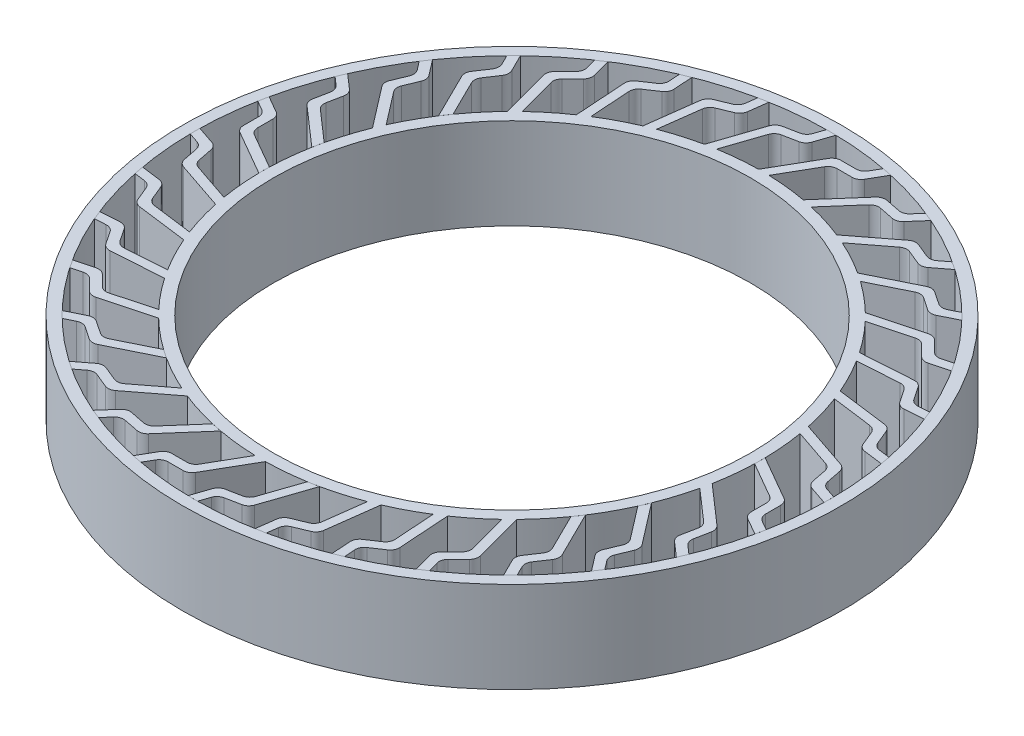
SolidWorks part; units mm, degrees
ref_plane "Alzado" through (0, 0, 0) normal (0, 0, 1) x (1, 0, 0)
ref_plane "Planta" through (0, 0, 0) normal (0, 1, 0) x (1, 0, 0)
ref_plane "Vista lateral" through (0, 0, 0) normal (1, 0, 0) x (0, 0, -1)
sketch "Croquis1" plane through (0, 0, 0) normal (0, 1, 0) x (1, 0, 0)
  line L0 (0, 279.5) -> (0, -279.5) construction
  line L1 (-279.5, 0) -> (279.5, 0) construction
  line L2 (-2.8965, 219.4809) -> (6.296, 219.4097)
  line L3 (51.4013, 274.7329) -> (59.6687, 273.0566)
  line L4 (-2.8965, 219.4809) -> (19.5628, 258.4505)
  line L5 (51.257, 258.4611) -> (59.6687, 273.0566)
  line L6 (51.4013, 274.7329) -> (46.6341, 266.4611)
  line L7 (39.7028, 262.4558) -> (26.4941, 262.4558)
  line L8 (104.0114, 259.4261) -> (111.7929, 256.1691)
  line L9 (100.6953, 243.4952) -> (111.7929, 256.1691)
  line L10 (44.3257, 254.4558) -> (31.117, 254.4558)
  line L11 (24.1857, 250.4505) -> (6.296, 219.4097)
  line L12 (93.1159, 240.919) -> (80.1609, 243.4959)
  line L13 (72.5814, 240.9198) -> (48.9797, 213.9655)
  line L14 (39.9778, 215.8287) -> (48.9797, 213.9655)
  line L15 (39.9778, 215.8287) -> (69.6081, 249.6679)
  line L16 (90.1425, 249.6672) -> (77.1876, 252.2441)
  line L17 (104.0114, 259.4261) -> (97.722, 252.2433)
  line L18 (152.6243, 234.1497) -> (159.6209, 229.4372)
  line L19 (146.2641, 219.1718) -> (159.6209, 229.4372)
  line L20 (138.3276, 218.1238) -> (126.1243, 223.1786)
  line L21 (118.1879, 222.1306) -> (89.7812, 200.2987)
  line L22 (81.3157, 203.8823) -> (89.7812, 200.2987)
  line L23 (81.3157, 203.8823) -> (116.9784, 231.2908)
  line L24 (137.1181, 227.284) -> (124.9148, 232.3387)
  line L25 (152.6243, 234.1497) -> (145.0545, 228.3319)
  line L26 (195.372, 199.875) -> (201.3148, 193.8881)
  line L27 (186.2119, 186.4257) -> (201.3148, 193.8881)
  line L28 (178.2235, 186.9463) -> (167.2409, 194.2846)
  line L29 (159.2525, 194.8051) -> (127.1324, 178.9346)
  line L30 (119.5287, 184.1009) -> (127.1324, 178.9346)
  line L31 (119.5287, 184.1009) -> (159.8533, 204.0252)
  line L32 (178.8243, 196.1664) -> (167.8417, 203.5047)
  line L33 (195.372, 199.875) -> (186.8127, 195.6458)
  line L34 (230.6117, 157.9193) -> (235.2723, 150.888)
  line L35 (219.0038, 146.5155) -> (235.2723, 150.888)
  line L36 (211.2704, 148.5844) -> (201.9305, 157.9244)
  line L37 (194.1971, 159.9934) -> (159.598, 150.6941)
  line L38 (153.1483, 157.2446) -> (159.598, 150.6941)
  line L39 (153.1483, 157.2446) -> (196.5851, 168.9191)
  line L40 (213.6584, 157.5102) -> (204.3184, 166.8502)
  line L41 (230.6117, 157.9193) -> (221.3917, 155.4412)
  line L42 (256.9891, 109.8948) -> (260.1884, 102.0894)
  line L43 (243.3794, 100.9747) -> (260.1884, 102.0894)
  line L44 (236.1983, 104.5126) -> (228.8599, 115.4953)
  line L45 (221.6788, 119.0332) -> (185.9304, 116.6626)
  line L46 (180.8825, 124.3454) -> (185.9304, 116.6626)
  line L47 (180.8825, 124.3454) -> (225.7623, 127.3215)
  line L48 (240.2817, 112.801) -> (232.9434, 123.7836)
  line L49 (256.9891, 109.8948) -> (247.4628, 109.2631)
  line L50 (273.4905, 57.6471) -> (275.1056, 49.3675)
  line L51 (258.4022, 51.5535) -> (275.1056, 49.3675)
  line L52 (252.0492, 56.4244) -> (246.9945, 68.6277)
  line L53 (240.6416, 73.4986) -> (205.1175, 78.1477)
  line L54 (201.6655, 86.6677) -> (205.1175, 78.1477)
  line L55 (201.6655, 86.6677) -> (246.2635, 80.8311)
  line L56 (257.6712, 63.7569) -> (252.6164, 75.9602)
  line L57 (273.4905, 57.6471) -> (264.0241, 58.886)
  line L58 (279.4819, 3.1841) -> (279.4507, -5.2515)
  line L59 (263.4946, 0.1512) -> (279.4507, -5.2515)
  line L60 (258.214, 6.1679) -> (255.6371, 19.1228)
  line L61 (250.3566, 25.1395) -> (216.4221, 36.6297)
  line L62 (214.6985, 45.6594) -> (216.4221, 36.6297)
  line L63 (214.6985, 45.6594) -> (257.301, 31.2343)
  line L64 (265.1584, 12.2627) -> (262.5815, 25.2176)
  line L65 (279.4819, 3.1841) -> (270.439, 6.246)
  line L66 (274.7329, -51.4013) -> (273.0566, -59.6687)
  line L67 (258.4611, -51.257) -> (273.0566, -59.6687)
  line L68 (254.4558, -44.3257) -> (254.4558, -31.117)
  line L69 (250.4505, -24.1857) -> (219.4097, -6.296)
  line L70 (219.4809, 2.8965) -> (219.4097, -6.296)
  line L71 (219.4809, 2.8965) -> (258.4505, -19.5628)
  line L72 (262.4558, -39.7028) -> (262.4558, -26.4941)
  line L73 (274.7329, -51.4013) -> (266.4611, -46.6341)
  line L74 (259.4261, -104.0114) -> (256.1691, -111.7929)
  line L75 (243.4952, -100.6953) -> (256.1691, -111.7929)
  line L76 (240.919, -93.1159) -> (243.4959, -80.1609)
  line L77 (240.9198, -72.5814) -> (213.9655, -48.9797)
  line L78 (215.8287, -39.9778) -> (213.9655, -48.9797)
  line L79 (215.8287, -39.9778) -> (249.6679, -69.6081)
  line L80 (249.6672, -90.1425) -> (252.2441, -77.1876)
  line L81 (259.4261, -104.0114) -> (252.2433, -97.722)
  line L82 (234.1497, -152.6243) -> (229.4372, -159.6209)
  line L83 (219.1718, -146.2641) -> (229.4372, -159.6209)
  line L84 (218.1238, -138.3276) -> (223.1786, -126.1243)
  line L85 (222.1306, -118.1879) -> (200.2987, -89.7812)
  line L86 (203.8823, -81.3157) -> (200.2987, -89.7812)
  line L87 (203.8823, -81.3157) -> (231.2908, -116.9784)
  line L88 (227.284, -137.1181) -> (232.3387, -124.9148)
  line L89 (234.1497, -152.6243) -> (228.3319, -145.0545)
  line L90 (199.875, -195.372) -> (193.8881, -201.3148)
  line L91 (186.4257, -186.2119) -> (193.8881, -201.3148)
  line L92 (186.9463, -178.2235) -> (194.2846, -167.2409)
  line L93 (194.8051, -159.2525) -> (178.9346, -127.1324)
  line L94 (184.1009, -119.5287) -> (178.9346, -127.1324)
  line L95 (184.1009, -119.5287) -> (204.0252, -159.8533)
  line L96 (196.1664, -178.8243) -> (203.5047, -167.8417)
  line L97 (199.875, -195.372) -> (195.6458, -186.8127)
  line L98 (157.9193, -230.6117) -> (150.888, -235.2723)
  line L99 (146.5155, -219.0038) -> (150.888, -235.2723)
  line L100 (148.5844, -211.2704) -> (157.9244, -201.9305)
  line L101 (159.9934, -194.1971) -> (150.6941, -159.598)
  line L102 (157.2446, -153.1483) -> (150.6941, -159.598)
  line L103 (157.2446, -153.1483) -> (168.9191, -196.5851)
  line L104 (157.5102, -213.6584) -> (166.8502, -204.3184)
  line L105 (157.9193, -230.6117) -> (155.4412, -221.3917)
  line L106 (109.8948, -256.9891) -> (102.0894, -260.1884)
  line L107 (100.9747, -243.3794) -> (102.0894, -260.1884)
  line L108 (104.5126, -236.1983) -> (115.4953, -228.8599)
  line L109 (119.0332, -221.6788) -> (116.6626, -185.9304)
  line L110 (124.3454, -180.8825) -> (116.6626, -185.9304)
  line L111 (124.3454, -180.8825) -> (127.3215, -225.7623)
  line L112 (112.801, -240.2817) -> (123.7836, -232.9434)
  line L113 (109.8948, -256.9891) -> (109.2631, -247.4628)
  line L114 (57.6471, -273.4905) -> (49.3675, -275.1056)
  line L115 (51.5535, -258.4022) -> (49.3675, -275.1056)
  line L116 (56.4244, -252.0492) -> (68.6277, -246.9945)
  line L117 (73.4986, -240.6416) -> (78.1477, -205.1175)
  line L118 (86.6677, -201.6655) -> (78.1477, -205.1175)
  line L119 (86.6677, -201.6655) -> (80.8311, -246.2635)
  line L120 (63.7569, -257.6712) -> (75.9602, -252.6164)
  line L121 (57.6471, -273.4905) -> (58.886, -264.0241)
  line L122 (3.1841, -279.4819) -> (-5.2515, -279.4507)
  line L123 (0.1512, -263.4946) -> (-5.2515, -279.4507)
  line L124 (6.1679, -258.214) -> (19.1228, -255.6371)
  line L125 (25.1395, -250.3566) -> (36.6297, -216.4221)
  line L126 (45.6594, -214.6985) -> (36.6297, -216.4221)
  line L127 (45.6594, -214.6985) -> (31.2343, -257.301)
  line L128 (12.2627, -265.1584) -> (25.2176, -262.5815)
  line L129 (3.1841, -279.4819) -> (6.246, -270.439)
  line L130 (-51.4013, -274.7329) -> (-59.6687, -273.0566)
  line L131 (-51.257, -258.4611) -> (-59.6687, -273.0566)
  line L132 (-44.3257, -254.4558) -> (-31.117, -254.4558)
  line L133 (-24.1857, -250.4505) -> (-6.296, -219.4097)
  line L134 (2.8965, -219.4809) -> (-6.296, -219.4097)
  line L135 (2.8965, -219.4809) -> (-19.5628, -258.4505)
  line L136 (-39.7028, -262.4558) -> (-26.4941, -262.4558)
  line L137 (-51.4013, -274.7329) -> (-46.6341, -266.4611)
  line L138 (-104.0114, -259.4261) -> (-111.7929, -256.1691)
  line L139 (-100.6953, -243.4952) -> (-111.7929, -256.1691)
  line L140 (-93.1159, -240.919) -> (-80.1609, -243.4959)
  line L141 (-72.5814, -240.9198) -> (-48.9797, -213.9655)
  line L142 (-39.9778, -215.8287) -> (-48.9797, -213.9655)
  line L143 (-39.9778, -215.8287) -> (-69.6081, -249.6679)
  line L144 (-90.1425, -249.6672) -> (-77.1876, -252.2441)
  line L145 (-104.0114, -259.4261) -> (-97.722, -252.2433)
  line L146 (-152.6243, -234.1497) -> (-159.6209, -229.4372)
  line L147 (-146.2641, -219.1718) -> (-159.6209, -229.4372)
  line L148 (-138.3276, -218.1238) -> (-126.1243, -223.1786)
  line L149 (-118.1879, -222.1306) -> (-89.7812, -200.2987)
  line L150 (-81.3157, -203.8823) -> (-89.7812, -200.2987)
  line L151 (-81.3157, -203.8823) -> (-116.9784, -231.2908)
  line L152 (-137.1181, -227.284) -> (-124.9148, -232.3387)
  line L153 (-152.6243, -234.1497) -> (-145.0545, -228.3319)
  line L154 (-195.372, -199.875) -> (-201.3148, -193.8881)
  line L155 (-186.2119, -186.4257) -> (-201.3148, -193.8881)
  line L156 (-178.2235, -186.9463) -> (-167.2409, -194.2846)
  line L157 (-159.2525, -194.8051) -> (-127.1324, -178.9346)
  line L158 (-119.5287, -184.1009) -> (-127.1324, -178.9346)
  line L159 (-119.5287, -184.1009) -> (-159.8533, -204.0252)
  line L160 (-178.8243, -196.1664) -> (-167.8417, -203.5047)
  line L161 (-195.372, -199.875) -> (-186.8127, -195.6458)
  line L162 (-230.6117, -157.9193) -> (-235.2723, -150.888)
  line L163 (-219.0038, -146.5155) -> (-235.2723, -150.888)
  line L164 (-211.2704, -148.5844) -> (-201.9305, -157.9244)
  line L165 (-194.1971, -159.9934) -> (-159.598, -150.6941)
  line L166 (-153.1483, -157.2446) -> (-159.598, -150.6941)
  line L167 (-153.1483, -157.2446) -> (-196.5851, -168.9191)
  line L168 (-213.6584, -157.5102) -> (-204.3184, -166.8502)
  line L169 (-230.6117, -157.9193) -> (-221.3917, -155.4412)
  line L170 (-256.9891, -109.8948) -> (-260.1884, -102.0894)
  line L171 (-243.3794, -100.9747) -> (-260.1884, -102.0894)
  line L172 (-236.1983, -104.5126) -> (-228.8599, -115.4953)
  line L173 (-221.6788, -119.0332) -> (-185.9304, -116.6626)
  line L174 (-180.8825, -124.3454) -> (-185.9304, -116.6626)
  line L175 (-180.8825, -124.3454) -> (-225.7623, -127.3215)
  line L176 (-240.2817, -112.801) -> (-232.9434, -123.7836)
  line L177 (-256.9891, -109.8948) -> (-247.4628, -109.2631)
  line L178 (-273.4905, -57.6471) -> (-275.1056, -49.3675)
  line L179 (-258.4022, -51.5535) -> (-275.1056, -49.3675)
  line L180 (-252.0492, -56.4244) -> (-246.9945, -68.6277)
  line L181 (-240.6416, -73.4986) -> (-205.1175, -78.1477)
  line L182 (-201.6655, -86.6677) -> (-205.1175, -78.1477)
  line L183 (-201.6655, -86.6677) -> (-246.2635, -80.8311)
  line L184 (-257.6712, -63.7569) -> (-252.6164, -75.9602)
  line L185 (-273.4905, -57.6471) -> (-264.0241, -58.886)
  line L186 (-279.4819, -3.1841) -> (-279.4507, 5.2515)
  line L187 (-263.4946, -0.1512) -> (-279.4507, 5.2515)
  line L188 (-258.214, -6.1679) -> (-255.6371, -19.1228)
  line L189 (-250.3566, -25.1395) -> (-216.4221, -36.6297)
  line L190 (-214.6985, -45.6594) -> (-216.4221, -36.6297)
  line L191 (-214.6985, -45.6594) -> (-257.301, -31.2343)
  line L192 (-265.1584, -12.2627) -> (-262.5815, -25.2176)
  line L193 (-279.4819, -3.1841) -> (-270.439, -6.246)
  line L194 (-274.7329, 51.4013) -> (-273.0566, 59.6687)
  line L195 (-258.4611, 51.257) -> (-273.0566, 59.6687)
  line L196 (-254.4558, 44.3257) -> (-254.4558, 31.117)
  line L197 (-250.4505, 24.1857) -> (-219.4097, 6.296)
  line L198 (-219.4809, -2.8965) -> (-219.4097, 6.296)
  line L199 (-219.4809, -2.8965) -> (-258.4505, 19.5628)
  line L200 (-262.4558, 39.7028) -> (-262.4558, 26.4941)
  line L201 (-274.7329, 51.4013) -> (-266.4611, 46.6341)
  line L202 (-259.4261, 104.0114) -> (-256.1691, 111.7929)
  line L203 (-243.4952, 100.6953) -> (-256.1691, 111.7929)
  line L204 (-240.919, 93.1159) -> (-243.4959, 80.1609)
  line L205 (-240.9198, 72.5814) -> (-213.9655, 48.9797)
  line L206 (-215.8287, 39.9778) -> (-213.9655, 48.9797)
  line L207 (-215.8287, 39.9778) -> (-249.6679, 69.6081)
  line L208 (-249.6672, 90.1425) -> (-252.2441, 77.1876)
  line L209 (-259.4261, 104.0114) -> (-252.2433, 97.722)
  line L210 (-234.1497, 152.6243) -> (-229.4372, 159.6209)
  line L211 (-219.1718, 146.2641) -> (-229.4372, 159.6209)
  line L212 (-218.1238, 138.3276) -> (-223.1786, 126.1243)
  line L213 (-222.1306, 118.1879) -> (-200.2987, 89.7812)
  line L214 (-203.8823, 81.3157) -> (-200.2987, 89.7812)
  line L215 (-203.8823, 81.3157) -> (-231.2908, 116.9784)
  line L216 (-227.284, 137.1181) -> (-232.3387, 124.9148)
  line L217 (-234.1497, 152.6243) -> (-228.3319, 145.0545)
  line L218 (-199.875, 195.372) -> (-193.8881, 201.3148)
  line L219 (-186.4257, 186.2119) -> (-193.8881, 201.3148)
  line L220 (-186.9463, 178.2235) -> (-194.2846, 167.2409)
  line L221 (-194.8051, 159.2525) -> (-178.9346, 127.1324)
  line L222 (-184.1009, 119.5287) -> (-178.9346, 127.1324)
  line L223 (-184.1009, 119.5287) -> (-204.0252, 159.8533)
  line L224 (-196.1664, 178.8243) -> (-203.5047, 167.8417)
  line L225 (-199.875, 195.372) -> (-195.6458, 186.8127)
  line L226 (-157.9193, 230.6117) -> (-150.888, 235.2723)
  line L227 (-146.5155, 219.0038) -> (-150.888, 235.2723)
  line L228 (-148.5844, 211.2704) -> (-157.9244, 201.9305)
  line L229 (-159.9934, 194.1971) -> (-150.6941, 159.598)
  line L230 (-157.2446, 153.1483) -> (-150.6941, 159.598)
  line L231 (-157.2446, 153.1483) -> (-168.9191, 196.5851)
  line L232 (-157.5102, 213.6584) -> (-166.8502, 204.3184)
  line L233 (-157.9193, 230.6117) -> (-155.4412, 221.3917)
  line L234 (-109.8948, 256.9891) -> (-102.0894, 260.1884)
  line L235 (-100.9747, 243.3794) -> (-102.0894, 260.1884)
  line L236 (-104.5126, 236.1983) -> (-115.4953, 228.8599)
  line L237 (-119.0332, 221.6788) -> (-116.6626, 185.9304)
  line L238 (-124.3454, 180.8825) -> (-116.6626, 185.9304)
  line L239 (-124.3454, 180.8825) -> (-127.3215, 225.7623)
  line L240 (-112.801, 240.2817) -> (-123.7836, 232.9434)
  line L241 (-109.8948, 256.9891) -> (-109.2631, 247.4628)
  line L242 (-57.6471, 273.4905) -> (-49.3675, 275.1056)
  line L243 (-51.5535, 258.4022) -> (-49.3675, 275.1056)
  line L244 (-56.4244, 252.0492) -> (-68.6277, 246.9945)
  line L245 (-73.4986, 240.6416) -> (-78.1477, 205.1175)
  line L246 (-86.6677, 201.6655) -> (-78.1477, 205.1175)
  line L247 (-86.6677, 201.6655) -> (-80.8311, 246.2635)
  line L248 (-63.7569, 257.6712) -> (-75.9602, 252.6164)
  line L249 (-57.6471, 273.4905) -> (-58.886, 264.0241)
  line L250 (-3.1841, 279.4819) -> (5.2515, 279.4507)
  line L251 (-0.1512, 263.4946) -> (5.2515, 279.4507)
  line L252 (-6.1679, 258.214) -> (-19.1228, 255.6371)
  line L253 (-25.1395, 250.3566) -> (-36.6297, 216.4221)
  line L254 (-45.6594, 214.6985) -> (-36.6297, 216.4221)
  line L255 (-45.6594, 214.6985) -> (-31.2343, 257.301)
  line L256 (-12.2627, 265.1584) -> (-25.2176, 262.5815)
  line L257 (-3.1841, 279.4819) -> (-6.246, 270.439)
  circle A0 centre (0, 0) radius 279.5
  circle A1 centre (0, 0) radius 219.5
  arc A2 (51.257, 258.4611) -> (44.3257, 254.4558) centre (44.3257, 262.4558) cw
  arc A3 (46.6341, 266.4611) -> (39.7028, 262.4558) centre (39.7028, 270.4558) cw
  arc A4 (31.117, 254.4558) -> (24.1857, 250.4505) centre (31.117, 246.4558) ccw
  arc A5 (26.4941, 262.4558) -> (19.5628, 258.4505) centre (26.4941, 254.4558) ccw
  arc A6 (100.6953, 243.4952) -> (93.1159, 240.919) centre (94.6766, 248.7653) cw
  arc A7 (80.1609, 243.4959) -> (72.5814, 240.9198) centre (78.6002, 235.6496) ccw
  arc A8 (77.1876, 252.2441) -> (69.6081, 249.6679) centre (75.6269, 244.3978) ccw
  arc A9 (97.722, 252.2433) -> (90.1425, 249.6672) centre (91.7032, 257.5135) cw
  arc A10 (146.2641, 219.1718) -> (138.3276, 218.1238) centre (141.3891, 225.5149) cw
  arc A11 (126.1243, 223.1786) -> (118.1879, 222.1306) centre (123.0629, 215.7876) ccw
  arc A12 (124.9148, 232.3387) -> (116.9784, 231.2908) centre (121.8534, 224.9477) ccw
  arc A13 (145.0545, 228.3319) -> (137.1181, 227.284) centre (140.1796, 234.675) cw
  arc A14 (186.2119, 186.4257) -> (178.2235, 186.9463) centre (182.6681, 193.598) cw
  arc A15 (167.2409, 194.2846) -> (159.2525, 194.8051) centre (162.7963, 187.6329) ccw
  arc A16 (167.8417, 203.5047) -> (159.8533, 204.0252) centre (163.3971, 196.853) ccw
  arc A17 (186.8127, 195.6458) -> (178.8243, 196.1664) centre (183.2689, 202.8181) cw
  arc A18 (219.0038, 146.5155) -> (211.2704, 148.5844) centre (216.9273, 154.2413) cw
  arc A19 (201.9305, 157.9244) -> (194.1971, 159.9934) centre (196.2736, 152.2676) ccw
  arc A20 (204.3184, 166.8502) -> (196.5851, 168.9191) centre (198.6616, 161.1933) ccw
  arc A21 (221.3917, 155.4412) -> (213.6584, 157.5102) centre (219.3153, 163.167) cw
  arc A22 (243.3794, 100.9747) -> (236.1983, 104.5126) centre (242.8501, 108.9572) cw
  arc A23 (228.8599, 115.4953) -> (221.6788, 119.0332) centre (222.2082, 111.0507) ccw
  arc A24 (232.9434, 123.7836) -> (225.7623, 127.3215) centre (226.2916, 119.3391) ccw
  arc A25 (247.4628, 109.2631) -> (240.2817, 112.801) centre (246.9335, 117.2455) cw
  arc A26 (258.4022, 51.5535) -> (252.0492, 56.4244) centre (259.4403, 59.4859) cw
  arc A27 (246.9945, 68.6277) -> (240.6416, 73.4986) centre (239.6034, 65.5662) ccw
  arc A28 (252.6164, 75.9602) -> (246.2635, 80.8311) centre (245.2254, 72.8987) ccw
  arc A29 (264.0241, 58.886) -> (257.6712, 63.7569) centre (265.0622, 66.8184) cw
  arc A30 (263.4946, 0.1512) -> (258.214, 6.1679) centre (266.0603, 7.7286) cw
  arc A31 (255.6371, 19.1228) -> (250.3566, 25.1395) centre (247.7909, 17.5621) ccw
  arc A32 (262.5815, 25.2176) -> (257.301, 31.2343) centre (254.7353, 23.6569) ccw
  arc A33 (270.439, 6.246) -> (265.1584, 12.2627) centre (273.0047, 13.8234) cw
  arc A34 (258.4611, -51.257) -> (254.4558, -44.3257) centre (262.4558, -44.3257) cw
  arc A35 (254.4558, -31.117) -> (250.4505, -24.1857) centre (246.4558, -31.117) ccw
  arc A36 (262.4558, -26.4941) -> (258.4505, -19.5628) centre (254.4558, -26.4941) ccw
  arc A37 (266.4611, -46.6341) -> (262.4558, -39.7028) centre (270.4558, -39.7028) cw
  arc A38 (243.4952, -100.6953) -> (240.919, -93.1159) centre (248.7653, -94.6766) cw
  arc A39 (243.4959, -80.1609) -> (240.9198, -72.5814) centre (235.6496, -78.6002) ccw
  arc A40 (252.2441, -77.1876) -> (249.6679, -69.6081) centre (244.3978, -75.6269) ccw
  arc A41 (252.2433, -97.722) -> (249.6672, -90.1425) centre (257.5135, -91.7032) cw
  arc A42 (219.1718, -146.2641) -> (218.1238, -138.3276) centre (225.5149, -141.3891) cw
  arc A43 (223.1786, -126.1243) -> (222.1306, -118.1879) centre (215.7876, -123.0629) ccw
  arc A44 (232.3387, -124.9148) -> (231.2908, -116.9784) centre (224.9477, -121.8534) ccw
  arc A45 (228.3319, -145.0545) -> (227.284, -137.1181) centre (234.675, -140.1796) cw
  arc A46 (186.4257, -186.2119) -> (186.9463, -178.2235) centre (193.598, -182.6681) cw
  arc A47 (194.2846, -167.2409) -> (194.8051, -159.2525) centre (187.6329, -162.7963) ccw
  arc A48 (203.5047, -167.8417) -> (204.0252, -159.8533) centre (196.853, -163.3971) ccw
  arc A49 (195.6458, -186.8127) -> (196.1664, -178.8243) centre (202.8181, -183.2689) cw
  arc A50 (146.5155, -219.0038) -> (148.5844, -211.2704) centre (154.2413, -216.9273) cw
  arc A51 (157.9244, -201.9305) -> (159.9934, -194.1971) centre (152.2676, -196.2736) ccw
  arc A52 (166.8502, -204.3184) -> (168.9191, -196.5851) centre (161.1933, -198.6616) ccw
  arc A53 (155.4412, -221.3917) -> (157.5102, -213.6584) centre (163.167, -219.3153) cw
  arc A54 (100.9747, -243.3794) -> (104.5126, -236.1983) centre (108.9572, -242.8501) cw
  arc A55 (115.4953, -228.8599) -> (119.0332, -221.6788) centre (111.0507, -222.2082) ccw
  arc A56 (123.7836, -232.9434) -> (127.3215, -225.7623) centre (119.3391, -226.2916) ccw
  arc A57 (109.2631, -247.4628) -> (112.801, -240.2817) centre (117.2455, -246.9335) cw
  arc A58 (51.5535, -258.4022) -> (56.4244, -252.0492) centre (59.4859, -259.4403) cw
  arc A59 (68.6277, -246.9945) -> (73.4986, -240.6416) centre (65.5662, -239.6034) ccw
  arc A60 (75.9602, -252.6164) -> (80.8311, -246.2635) centre (72.8987, -245.2254) ccw
  arc A61 (58.886, -264.0241) -> (63.7569, -257.6712) centre (66.8184, -265.0622) cw
  arc A62 (0.1512, -263.4946) -> (6.1679, -258.214) centre (7.7286, -266.0603) cw
  arc A63 (19.1228, -255.6371) -> (25.1395, -250.3566) centre (17.5621, -247.7909) ccw
  arc A64 (25.2176, -262.5815) -> (31.2343, -257.301) centre (23.6569, -254.7353) ccw
  arc A65 (6.246, -270.439) -> (12.2627, -265.1584) centre (13.8234, -273.0047) cw
  arc A66 (-51.257, -258.4611) -> (-44.3257, -254.4558) centre (-44.3257, -262.4558) cw
  arc A67 (-31.117, -254.4558) -> (-24.1857, -250.4505) centre (-31.117, -246.4558) ccw
  arc A68 (-26.4941, -262.4558) -> (-19.5628, -258.4505) centre (-26.4941, -254.4558) ccw
  arc A69 (-46.6341, -266.4611) -> (-39.7028, -262.4558) centre (-39.7028, -270.4558) cw
  arc A70 (-100.6953, -243.4952) -> (-93.1159, -240.919) centre (-94.6766, -248.7653) cw
  arc A71 (-80.1609, -243.4959) -> (-72.5814, -240.9198) centre (-78.6002, -235.6496) ccw
  arc A72 (-77.1876, -252.2441) -> (-69.6081, -249.6679) centre (-75.6269, -244.3978) ccw
  arc A73 (-97.722, -252.2433) -> (-90.1425, -249.6672) centre (-91.7032, -257.5135) cw
  arc A74 (-146.2641, -219.1718) -> (-138.3276, -218.1238) centre (-141.3891, -225.5149) cw
  arc A75 (-126.1243, -223.1786) -> (-118.1879, -222.1306) centre (-123.0629, -215.7876) ccw
  arc A76 (-124.9148, -232.3387) -> (-116.9784, -231.2908) centre (-121.8534, -224.9477) ccw
  arc A77 (-145.0545, -228.3319) -> (-137.1181, -227.284) centre (-140.1796, -234.675) cw
  arc A78 (-186.2119, -186.4257) -> (-178.2235, -186.9463) centre (-182.6681, -193.598) cw
  arc A79 (-167.2409, -194.2846) -> (-159.2525, -194.8051) centre (-162.7963, -187.6329) ccw
  arc A80 (-167.8417, -203.5047) -> (-159.8533, -204.0252) centre (-163.3971, -196.853) ccw
  arc A81 (-186.8127, -195.6458) -> (-178.8243, -196.1664) centre (-183.2689, -202.8181) cw
  arc A82 (-219.0038, -146.5155) -> (-211.2704, -148.5844) centre (-216.9273, -154.2413) cw
  arc A83 (-201.9305, -157.9244) -> (-194.1971, -159.9934) centre (-196.2736, -152.2676) ccw
  arc A84 (-204.3184, -166.8502) -> (-196.5851, -168.9191) centre (-198.6616, -161.1933) ccw
  arc A85 (-221.3917, -155.4412) -> (-213.6584, -157.5102) centre (-219.3153, -163.167) cw
  arc A86 (-243.3794, -100.9747) -> (-236.1983, -104.5126) centre (-242.8501, -108.9572) cw
  arc A87 (-228.8599, -115.4953) -> (-221.6788, -119.0332) centre (-222.2082, -111.0507) ccw
  arc A88 (-232.9434, -123.7836) -> (-225.7623, -127.3215) centre (-226.2916, -119.3391) ccw
  arc A89 (-247.4628, -109.2631) -> (-240.2817, -112.801) centre (-246.9335, -117.2455) cw
  arc A90 (-258.4022, -51.5535) -> (-252.0492, -56.4244) centre (-259.4403, -59.4859) cw
  arc A91 (-246.9945, -68.6277) -> (-240.6416, -73.4986) centre (-239.6034, -65.5662) ccw
  arc A92 (-252.6164, -75.9602) -> (-246.2635, -80.8311) centre (-245.2254, -72.8987) ccw
  arc A93 (-264.0241, -58.886) -> (-257.6712, -63.7569) centre (-265.0622, -66.8184) cw
  arc A94 (-263.4946, -0.1512) -> (-258.214, -6.1679) centre (-266.0603, -7.7286) cw
  arc A95 (-255.6371, -19.1228) -> (-250.3566, -25.1395) centre (-247.7909, -17.5621) ccw
  arc A96 (-262.5815, -25.2176) -> (-257.301, -31.2343) centre (-254.7353, -23.6569) ccw
  arc A97 (-270.439, -6.246) -> (-265.1584, -12.2627) centre (-273.0047, -13.8234) cw
  arc A98 (-258.4611, 51.257) -> (-254.4558, 44.3257) centre (-262.4558, 44.3257) cw
  arc A99 (-254.4558, 31.117) -> (-250.4505, 24.1857) centre (-246.4558, 31.117) ccw
  arc A100 (-262.4558, 26.4941) -> (-258.4505, 19.5628) centre (-254.4558, 26.4941) ccw
  arc A101 (-266.4611, 46.6341) -> (-262.4558, 39.7028) centre (-270.4558, 39.7028) cw
  arc A102 (-243.4952, 100.6953) -> (-240.919, 93.1159) centre (-248.7653, 94.6766) cw
  arc A103 (-243.4959, 80.1609) -> (-240.9198, 72.5814) centre (-235.6496, 78.6002) ccw
  arc A104 (-252.2441, 77.1876) -> (-249.6679, 69.6081) centre (-244.3978, 75.6269) ccw
  arc A105 (-252.2433, 97.722) -> (-249.6672, 90.1425) centre (-257.5135, 91.7032) cw
  arc A106 (-219.1718, 146.2641) -> (-218.1238, 138.3276) centre (-225.5149, 141.3891) cw
  arc A107 (-223.1786, 126.1243) -> (-222.1306, 118.1879) centre (-215.7876, 123.0629) ccw
  arc A108 (-232.3387, 124.9148) -> (-231.2908, 116.9784) centre (-224.9477, 121.8534) ccw
  arc A109 (-228.3319, 145.0545) -> (-227.284, 137.1181) centre (-234.675, 140.1796) cw
  arc A110 (-186.4257, 186.2119) -> (-186.9463, 178.2235) centre (-193.598, 182.6681) cw
  arc A111 (-194.2846, 167.2409) -> (-194.8051, 159.2525) centre (-187.6329, 162.7963) ccw
  arc A112 (-203.5047, 167.8417) -> (-204.0252, 159.8533) centre (-196.853, 163.3971) ccw
  arc A113 (-195.6458, 186.8127) -> (-196.1664, 178.8243) centre (-202.8181, 183.2689) cw
  arc A114 (-146.5155, 219.0038) -> (-148.5844, 211.2704) centre (-154.2413, 216.9273) cw
  arc A115 (-157.9244, 201.9305) -> (-159.9934, 194.1971) centre (-152.2676, 196.2736) ccw
  arc A116 (-166.8502, 204.3184) -> (-168.9191, 196.5851) centre (-161.1933, 198.6616) ccw
  arc A117 (-155.4412, 221.3917) -> (-157.5102, 213.6584) centre (-163.167, 219.3153) cw
  arc A118 (-100.9747, 243.3794) -> (-104.5126, 236.1983) centre (-108.9572, 242.8501) cw
  arc A119 (-115.4953, 228.8599) -> (-119.0332, 221.6788) centre (-111.0507, 222.2082) ccw
  arc A120 (-123.7836, 232.9434) -> (-127.3215, 225.7623) centre (-119.3391, 226.2916) ccw
  arc A121 (-109.2631, 247.4628) -> (-112.801, 240.2817) centre (-117.2455, 246.9335) cw
  arc A122 (-51.5535, 258.4022) -> (-56.4244, 252.0492) centre (-59.4859, 259.4403) cw
  arc A123 (-68.6277, 246.9945) -> (-73.4986, 240.6416) centre (-65.5662, 239.6034) ccw
  arc A124 (-75.9602, 252.6164) -> (-80.8311, 246.2635) centre (-72.8987, 245.2254) ccw
  arc A125 (-58.886, 264.0241) -> (-63.7569, 257.6712) centre (-66.8184, 265.0622) cw
  arc A126 (-0.1512, 263.4946) -> (-6.1679, 258.214) centre (-7.7286, 266.0603) cw
  arc A127 (-19.1228, 255.6371) -> (-25.1395, 250.3566) centre (-17.5621, 247.7909) ccw
  arc A128 (-25.2176, 262.5815) -> (-31.2343, 257.301) centre (-23.6569, 254.7353) ccw
  arc A129 (-6.246, 270.439) -> (-12.2627, 265.1584) centre (-13.8234, 273.0047) cw
  circle A130 centre (0, 0) radius 289.5
  circle A131 centre (0, 0) radius 209.5
  point P524 (0, 0)
  dimension "D1" = 559
  dimension "D2" = 439
  dimension "D6" = 8
  dimension "D8" = 579
  dimension "D9" = 419
  dimension "D4" = 8
  dimension "D3" = 8
  dimension "D5" = 8
  dimension "D7" = 32
extrude "Saliente-Extruir1" add sketch "Croquis1" along normal blind 80 contours L134 A1 L126 L118 L110 L102 L94 L86 L78 L70 L62 L54 L46 L38 L30 L22 L14 L2 L254 L246 L238 L230 L222 L214 L206 L198 L190 | L73 A37 L72 A36 L71 A1 L69 A35 L68 A34 L67 L66 | L89 A45 L88 A44 L87 A1 L85 A43 L84 A42 L83 L82 | L97 A49 L96 A48 L95 A1 L93 A47 L92 A46 L91 L90 | L129 A65 L128 A64 L127 A1 L125 A63 L124 A62 L123 L122 | L145 A73 L144 A72 L143 A1 L141 A71 L140 A70 L139 L138 | L161 A81 L160 A80 L159 A1 L157 A79 L156 A78 L155 L154 | L201 A101 L200 A100 L199 A1 L197 A99 L196 A98 L195 L194 | L209 A105 L208 A104 L207 A1 L205 A103 L204 A102 L203 L202 | L225 A113 L224 A112 L223 A1 L221 A111 L220 A110 L219 L218 | A130 A0 | L79 A40 L80 A41 L81 L74 L75 A38 L76 A39 L77 L78 | L63 A32 L64 A33 L65 L58 L59 A30 L60 A31 L61 L62 | L53 L54 L55 A28 L56 A29 L57 L50 L51 A26 L52 A27 | L47 A24 L48 A25 L49 L42 L43 A22 L44 A23 L45 L46 | L4 A5 L7 A3 L6 L3 L5 A2 L10 A4 L11 L2 | L15 A8 L16 A9 L17 L8 L9 A6 L12 A7 L13 L14 | L23 A12 L24 A13 L25 L18 L19 A10 L20 A11 L21 L22 | L31 A16 L32 A17 L33 L26 L27 A14 L28 A15 L29 L30 | L39 A20 L40 A21 L41 L34 L35 A18 L36 A19 L37 L38 | L101 L102 L103 A52 L104 A53 L105 L98 L99 A50 L100 A51 | L109 L110 L111 A56 L112 A57 L113 L106 L107 A54 L108 A55 | L117 L118 L119 A60 L120 A61 L121 L114 L115 A58 L116 A59 | L133 L134 L135 A68 L136 A69 L137 L130 L131 A66 L132 A67 | L150 L149 A75 L148 A74 L147 L146 L153 A77 L152 A76 L151 | L167 A84 L168 A85 L169 L162 L163 A82 L164 A83 L165 L166 | L173 L174 L175 A88 L176 A89 L177 L170 L171 A86 L172 A87 | L181 L182 L183 A92 L184 A93 L185 L178 L179 A90 L180 A91 | L189 L190 L191 A96 L192 A97 L193 L186 L187 A94 L188 A95 | L215 A108 L216 A109 L217 L210 L211 A106 L212 A107 L213 L214 | L231 A116 L232 A117 L233 L226 L227 A114 L228 A115 L229 L230 | L237 L238 L239 A120 L240 A121 L241 L234 L235 A118 L236 A119 | L245 L246 L247 A124 L248 A125 L249 L242 L243 A122 L244 A123 | L255 A128 L256 A129 L257 L250 L251 A126 L252 A127 L253 L254 region at (1.6517, 0, -213.2376) region at (-182.2672, 0, -123.8398) region at (-215.7765, 0, -44.6608) region at (-220.3286, 0, -1.7066) region at (238.5487, 0, 9.0567) region at (216.9102, 0, 99.6669) region at (193.2939, 0, 140.071) region at (-123.8398, 0, 182.2672) region at (-44.6608, 0, 215.7765) region at (37.6664, 0, 235.7355) region at (-281.3117, 0, 0)
equation "\"Dr\"= 559"
equation "\"D1@Croquis1\"=\"Dr\""
equation "\"D2@Croquis1\"=\"Dr\" - 120"
equation "\"D8@Croquis1\"=\"Dr\" + 20"
equation "\"D9@Croquis1\"=\"Dr\" - 140"
